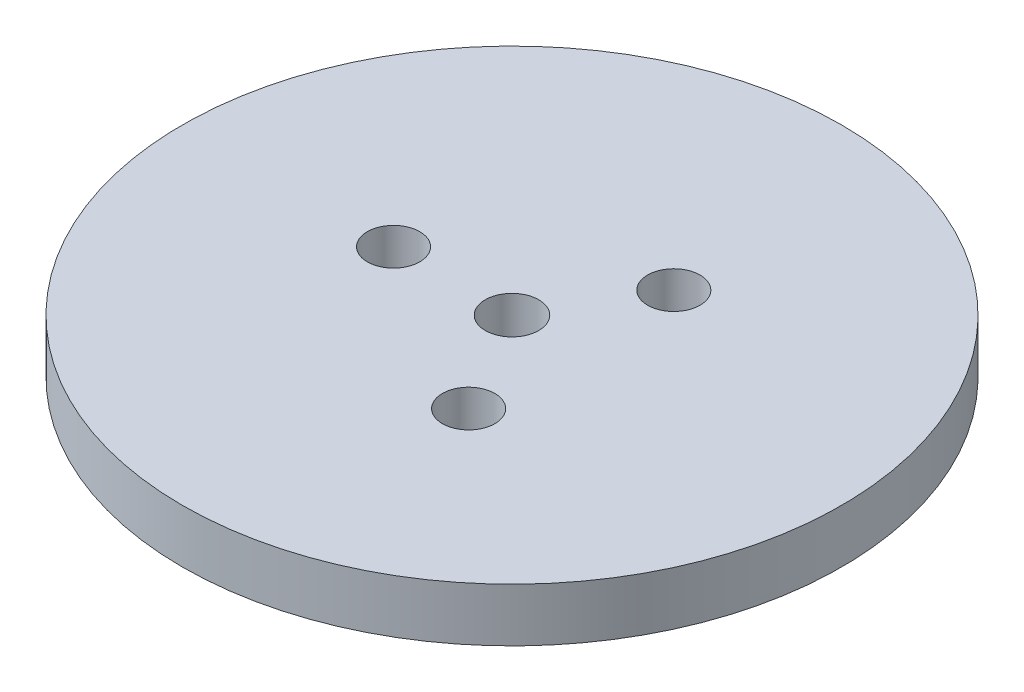
SolidWorks part; units mm, degrees
ref_plane "Front Plane" through (0, 0, 0) normal (0, 0, 1) x (1, 0, 0)
ref_plane "Top Plane" through (0, 0, 0) normal (0, 1, 0) x (1, 0, 0)
ref_plane "Right Plane" through (0, 0, 0) normal (1, 0, 0) x (0, 0, -1)
sketch "Sketch1" plane through (0, 0, 0) normal (0, 1, 0) x (1, 0, 0)
  circle A0 centre (0, 0) radius 92.5
  dimension "FLANGE_OD" = 185
extrude "Boss-Extrude1" add sketch "Sketch1" along normal blind 15
sketch "Sketch2" plane through (0, 0, 0) normal (0, 1, 0) x (1, 0, 0)
  circle A0 centre (0, 0) radius 7.5
  dimension "BORE_D" = 15
extrude "Cut-Extrude1" cut sketch "Sketch2" along normal through all
sketch "Sketch3" plane through (0, 15, 0) normal (0, 1, 0) x (1, 0, 0)
  circle A0 centre (0, 0) radius 33.2468 construction
  circle A1 centre (-33.2468, 0) radius 7.3569
  dimension "BOLT_D" = 14.7139
  dimension "BOLT_PCD" = 66.4937
extrude "Cut-Extrude2" cut sketch "Sketch3" against normal blind 14.2757
pattern_circular "CirPattern1" count 3 over 360 about axis through (0, 0, 0) along (0, 1, 0) of "Cut-Extrude2"
